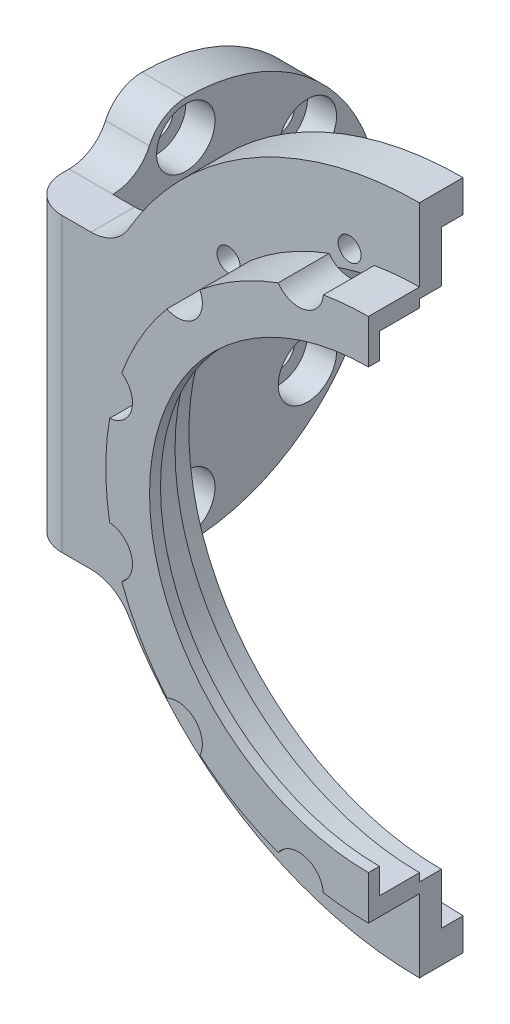
SolidWorks part; units mm, degrees
ref_plane "前视基准面" through (0, 0, 0) normal (0, 0, 1) x (1, 0, 0)
ref_plane "上视基准面" through (0, 0, 0) normal (0, 1, 0) x (1, 0, 0)
ref_plane "右视基准面" through (0, 0, 0) normal (1, 0, 0) x (0, 0, -1)
sketch "草图3" plane through (0, 0, 0) normal (0, 0, 1) x (1, 0, 0)
  circle A0 centre (0, 0) radius 34.6
  circle A1 centre (0, 0) radius 46
extrude "凸台-拉伸2" add sketch "草图3" along normal blind 3
ref_plane "基准面5" through (0, 0, 3) normal (0, 0, 1) x (1, 0, 0)
sketch "草图5" plane through (0, 0, 3) normal (0, 0, 1) x (1, 0, 0)
  circle A0 centre (0, 0) radius 33.5
  circle A1 centre (0, 0) radius 36
extrude "凸台-拉伸3" add sketch "草图5" along normal blind 5.49
sketch "草图2" plane through (0, 0, 0) normal (0, 0, 1) x (1, 0, 0)
  circle A0 centre (0, 0) radius 41.6
  circle A1 centre (0, 0) radius 46
extrude "凸台-拉伸1" add sketch "草图2" against normal blind 2.98
sketch "草图6" plane through (0, 0, 8.49) normal (0, 0, 1) x (1, 0, 0)
  circle A0 centre (0, 0) radius 30
  circle A1 centre (0, 0) radius 36
extrude "凸台-拉伸4" add sketch "草图6" along normal blind 1.5
sketch "草图8" plane through (0, 0, 0) normal (0, 0, 1) x (1, 0, 0)
  line L6 (-50, 20.008) -> (-45.0139, 20.008)
  line L8 (7.1335, 0) -> (-7.1335, 0) construction
  line L10 (-50, 20.008) -> (-50, -20.008)
  line L11 (-50, -20.008) -> (-45.0139, -20.008)
  arc A16 (-45.0139, 20.008) -> (-39.8396, 22.9958) centre (-45.0139, 25.9824) ccw
  arc A17 (-39.8396, 22.9958) -> (-39.8396, -22.9958) centre (0, 0) ccw
  arc A19 (-45.0139, -20.008) -> (-39.8396, -22.9958) centre (-45.0139, -25.9824) cw
extrude "凸台-拉伸5" add sketch "草图8" along normal blind 3 and the other way blind 2.98
hole_wizard "M3 螺旋的螺纹孔钻头2" positions "3D草图3" profile "草图12" hole size "M3x0.5" standard "BSI" end condition through all
sketch3d "3D草图3"
  line L2 (0, 0, 0) -> (0, 37, 0)
  line L3 (0, 0, 0) -> (11.5811, 0, 0)
  point P55 (9.5763, 35.7393, 3)
  point P76 (26.163, 26.163, 3)
  point P83 (35.7393, 9.5763, 3)
  point P96 (-35.7393, 9.5763, 3)
  point P97 (-26.163, 26.163, 3)
  point P98 (-9.5763, 35.7393, 3)
  point P99 (35.7393, -9.5763, 3)
  point P100 (26.163, -26.163, 3)
  point P101 (9.5763, -35.7393, 3)
  point P102 (-9.5763, -35.7393, 3)
  point P103 (-26.163, -26.163, 3)
  point P104 (-35.7393, -9.5763, 3)
sketch "草图12" plane through (-35.7393, -9.5763, 3) normal (1, 0, 0) x (0, -1, 0)
  line L0 (0, 0) -> (0, 5.98)
  line L1 (0, 5.98) -> (1.575, 5.98)
  line L2 (1.575, 5.98) -> (1.575, 0)
  line L5 (1.575, 0) -> (0, 0)
  line L11 (0, -6.35) -> (0, 107.95) construction
  dimension "通孔孔直径" = 3.15
  dimension "通孔孔深度" = 5.98
sketch "草图13" plane through (0, 0, 3) normal (0, 0, 1) x (1, 0, 0)
  line L0 (0, 0) -> (0, 10.9464)
  line L1 (0, 0) -> (8.3109, 0)
  circle A0 centre (-35.7393, 9.5763) radius 1.575
  circle A1 centre (-26.163, 26.163) radius 2.2
  circle A2 centre (-9.5763, 35.7393) radius 2.2
  circle A3 centre (-9.5763, -35.7393) radius 2.2
  circle A4 centre (-26.163, -26.163) radius 2.2
  circle A5 centre (-35.7393, -9.5763) radius 1.575
  circle A6 centre (9.5763, -35.7393) radius 2.2
  circle A7 centre (26.163, -26.163) radius 2.2
  circle A8 centre (9.5763, 35.7393) radius 2.2
  circle A9 centre (26.163, 26.163) radius 2.2
  circle A10 centre (35.7393, -9.5763) radius 1.575
  circle A11 centre (35.7393, 9.5763) radius 1.575
extrude "切除-拉伸1" cut sketch "草图13" along normal up to next contours A5 | A4 | A0 | A1 | A2 | A9 | A11 | A10 | A6 | A3 | A8 | A7 region at (-35.7393, 9.5763, 3) region at (-26.163, 26.163, 3) region at (-9.5763, 35.7393, 3) region at (-9.5763, -35.7393, 3) region at (-26.163, -26.163, 3) region at (-35.7393, -9.5763, 3) region at (9.5763, -35.7393, 3) region at (26.163, 26.163, 3) region at (35.7393, -9.5763, 3) region at (35.7393, 9.5763, 3)
sketch "草图25" plane through (0, 0, 3) normal (0, 0, 1) x (1, 0, 0)
  circle A0 centre (-9.5763, 35.7393) radius 3.4
  circle A1 centre (-26.163, 26.163) radius 3.4
  circle A2 centre (-35.7393, 9.5763) radius 3.4
  circle A3 centre (-35.7393, -9.5763) radius 3.4
  circle A4 centre (-26.163, -26.163) radius 3.4
  circle A5 centre (-9.5763, -35.7393) radius 3.4
extrude "切除-拉伸9" cut sketch "草图25" along normal blind 10
ref_plane "基准面6" through (-50, 0, 0) normal (-1, 0, 0) x (0, 0, 1)
sketch "草图26" plane through (-50, 0, 0) normal (-1, 0, 0) x (0, 0, 1)
  line L1 (-2.98, -20.008) -> (3, -20.008)
  line L5 (3, 20.008) -> (3, -20.008) construction
  line L6 (-2.98, 20.008) -> (3, 20.008)
  line L7 (3, 12.3737) -> (3, 23.0906) construction
  line L8 (3, 20.008) -> (3, -20.008)
  line L9 (-2.98, -20.008) -> (3, -20.008)
  arc A8 (-12.98, 26.5) -> (-12.98, -26.5) centre (-12.98, 0) ccw
  arc A9 (-12.98, 26.5) -> (-7.98, 23.254) centre (-12.98, 21.0261) cw
  arc A10 (-2.98, 20.008) -> (-7.98, 23.254) centre (-2.98, 25.4819) cw
  arc A11 (-2.98, -20.008) -> (-7.98, -23.254) centre (-2.98, -25.4819) ccw
  arc A12 (-12.98, -26.5) -> (-7.98, -23.254) centre (-12.98, -21.0261) ccw
extrude "凸台-拉伸7" add sketch "草图26" along normal blind 4 and the other way blind 2 contours A8 A12 A11 L1 L8 L6 A10 A9 region at (-50, 0, -16.9157)
sketch "草图27" plane through (0, 0, 0) normal (0, 0, 1) x (1, 0, 0)
  line L0 (0, 0) -> (0, 46)
  line L1 (0, -46) -> (0, 0)
  arc A0 (-39.8396, -22.9958) -> (-39.8396, 22.9958) centre (0, 0) ccw construction
  arc A1 (0, 46) -> (0, -46) centre (0, 0) cw
extrude "切除-拉伸10" cut sketch "草图27" against normal through all both and the other way through all
hole_wizard "M4 六角凹头盖的柱孔3" positions "3D草图5" profile "草图29" counterbore size "M4" standard "BSI" end condition up to next
sketch3d "3D草图5"
  point P0 (-48, 21.75, -12.98)
  point P4 (-48, 13.9806, -29.6415)
  point P25 (-50, 21.75, -12.98)
  point P26 (0, 0, 0)
  point P27 (0, 0, 0)
  point P28 (-48, -13.9806, -29.6415)
  point P29 (-48, -21.75, -12.98)
sketch "草图29" plane through (-48, 21.75, -12.98) normal (0, 1, 0) x (0, 0, -1)
  line L0 (0, 0) -> (0, 6)
  line L1 (0, 6) -> (2.25, 6)
  line L3 (2.25, 6) -> (2.25, 4)
  line L4 (2.25, 4) -> (4, 4)
  line L5 (4, 4) -> (4, 0)
  line L7 (4, 0) -> (0, 0)
  line L11 (0, -6.35) -> (0, 107.95) construction
  dimension "通孔孔直径" = 4.5
  dimension "通孔孔深度" = 6
  dimension "柱形沉头孔直径" = 8
  dimension "柱形沉头孔深度" = 4
fillet "圆角1" radius 5 1 edges at (-54, 0, 3)
